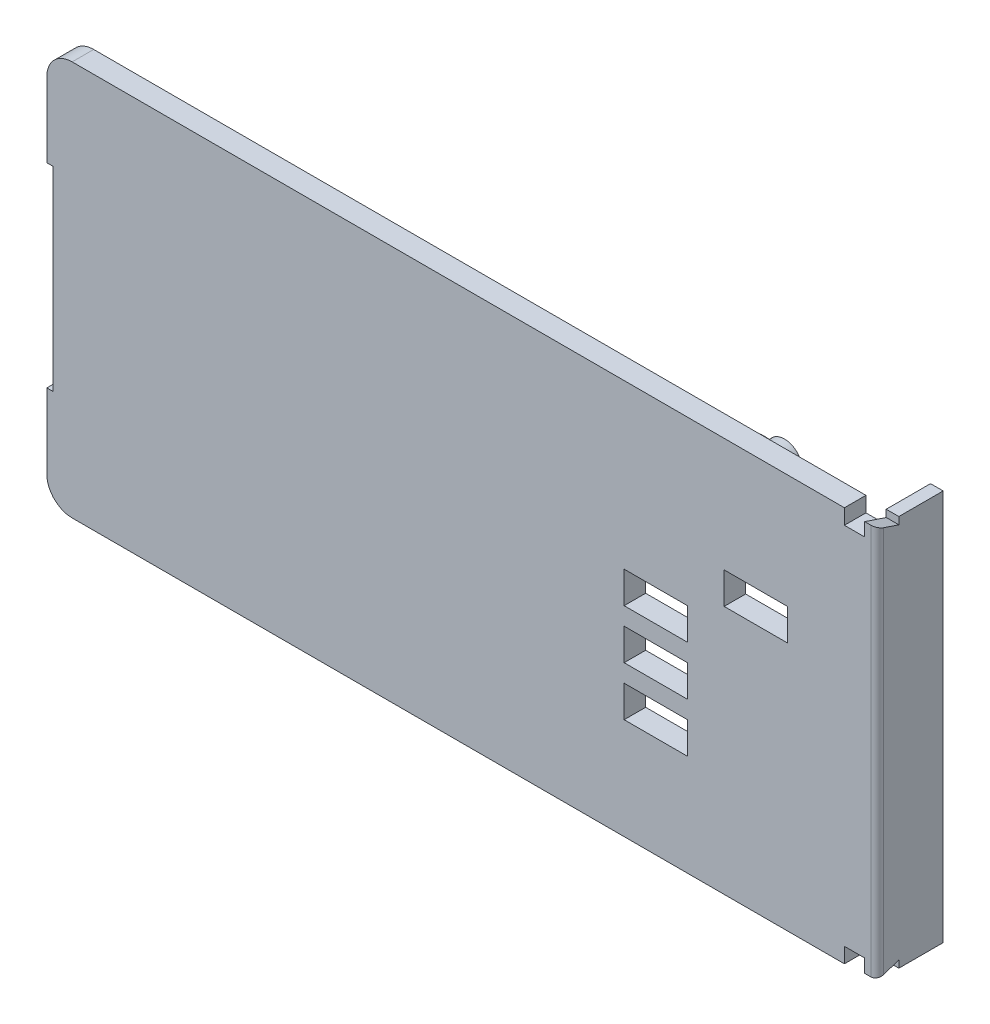
SolidWorks part; units mm, degrees
ref_plane "Front Plane" through (0, 0, 0) normal (0, 0, 1) x (1, 0, 0)
ref_plane "Top Plane" through (0, 0, 0) normal (0, 1, 0) x (1, 0, 0)
ref_plane "Right Plane" through (0, 0, 0) normal (1, 0, 0) x (0, 0, -1)
sketch "Sketch1" plane through (0, 0, 0) normal (0, 0, 1) x (1, 0, 0)
  line L0 (-32.3, 15.8) -> (-32.3, 7.5) construction
  line L1 (-32.1, 15.6) -> (30.9, 15.6)
  line L2 (-32.1, 15.6) -> (-32.1, 7.7)
  line L3 (-32.1, -15.6) -> (30.9, -15.6)
  line L4 (30.9, 15.6) -> (30.9, 14.4)
  line L5 (31.3, 15.8) -> (-32.3, 15.8) construction
  line L6 (-32.3, -15.8) -> (31.3, -15.8) construction
  line L7 (31.3, 15.8) -> (31.3, 14.8) construction
  line L8 (-32.1, 7.7) -> (-31.6, 7.7)
  line L9 (-31.6, 7.7) -> (-31.6, -7.7)
  line L10 (-31.6, -7.7) -> (-32.1, -7.7)
  line L11 (-31.8, 7.5) -> (-31.8, -7.5) construction
  line L12 (-31.8, 7.5) -> (-32.3, 7.5) construction
  line L13 (32.3, 15.8) -> (32.3, 14.8) construction
  line L14 (-32.1, -7.7) -> (-32.1, -15.6)
  line L15 (30.9, 14.4) -> (32.5008, 14.4)
  line L17 (32.5008, -14.4) -> (30.9, -14.4)
  line L18 (31.3, -14.8) -> (32.3, -14.8) construction
  line L19 (31.3, 14.8) -> (32.3, 14.8) construction
  line L20 (30.9, -14.4) -> (30.9, -15.6)
  line L21 (32.5008, 14.4) -> (32.5008, 15.45)
  line L22 (32.5008, 15.45) -> (33.5, 15.45)
  line L23 (33.5, 15.45) -> (33.5, -15.45)
  line L24 (33.5, -15.45) -> (32.5008, -15.45)
  line L25 (32.5008, -15.45) -> (32.5008, -14.4)
  line L26 (33.5, -15.8) -> (32.3, -15.8) construction
  line L27 (33.5, -16.5) -> (33.5, -15.8) construction
  line L28 (32.3, 15.8) -> (33.5, 15.8) construction
  point P12 (31.3, 15.3)
  point P19 (-31.8, 0)
  point P20 (-31.6, 0)
  dimension "D1" = 0.2
  dimension "D2" = 0.2
  dimension "D3" = 0.2
  dimension "D4" = 0.4
  dimension "D5" = 0.2
  dimension "D6" = 0.2
  dimension "D7" = 0.2
  dimension "D8" = 0.4
  dimension "D9" = 0.2008
  dimension "D10" = 0.35
  dimension "D11" = 0.35
  dimension "D12" = 0.4
extrude "Boss-Extrude1" add sketch "Sketch1" against normal offset from surface (1.7 mm away) 0.2 offset beyond the face yes
sketch "Sketch2" plane through (0, 0, -1.7) normal (0, 0, -1) x (-1, 0, 0)
  line L0 (32.1, 7.7) -> (32.1, 15.6) construction
  line L1 (32.1, 8.5791) -> (30.9, 8.5791)
  line L2 (32.1, 8.5791) -> (32.1, -8.7)
  line L3 (32.1, -8.7) -> (30.9, -8.7)
  line L4 (30.9, 8.5791) -> (30.9, -8.7)
  line L5 (31.6, -7.7) -> (31.6, 7.7) construction
  line L6 (32.1, -7.7) -> (31.6, -7.7) construction
  point P10 (32.1, -0.0604)
  point P11 (30.9, -0.0604)
  dimension "D1" = 0.7
  dimension "D2" = 1
extrude "Boss-Extrude2" add sketch "Sketch2" along normal offset from surface (3.5 mm away) 0.2
sketch "Sketch3" plane through (33.5, 0, 0) normal (1, 0, 0) x (0, 0, -1)
  line L0 (0, 15.45) -> (1.7, 14.8833)
  line L1 (0, -15.45) -> (0, 15.45) construction
  line L2 (1.7, 15.45) -> (1.7, -15.45) construction
  line L3 (1.7, 14.8833) -> (1.7, 15.45)
  line L4 (1.7, 15.45) -> (0, 15.45)
  line L5 (1.7, 15.45) -> (0, 15.45) construction
  line L6 (0, 15.8) -> (1.5, 15.3) construction
  line M1 (1.7, -15.45) -> (1.7, 15.45)
  line M2 (1.7, 15.45) -> (0, 15.45)
extrude "Cut-Extrude1" cut sketch "Sketch3" against normal up to surface (1.2 mm away) contours L0 M2 M1 region at (33.5, 15.2611, -1.1333)
mirror "Mirror1" about plane through (0, 0, 0) normal (0, 1, 0) of "Cut-Extrude1"
sketch "Sketch4" plane through (0, 0, -1.7) normal (0, 0, -1) x (-1, 0, 0)
  line L1 (-33.5, -15.45) -> (-32.5008, -15.45)
  line L2 (-33.5, -15.45) -> (-33.5, 15.45)
  line L3 (-33.5, 15.45) -> (-32.5008, 15.45)
  line L4 (-32.5008, -15.45) -> (-32.5008, 15.45)
extrude "Boss-Extrude3" add sketch "Sketch4" along normal offset from surface (3.5 mm away) 0.2
fillet "Fillet1" radius 2 2 edges at (-32.1, -15.6, -0.85) (-32.1, 15.6, -0.85)
fillet "Fillet2" radius 0.5 1 edges at (33.5, 0, 0)
sketch "Sketch5" plane through (0, 0, -1.7) normal (0, 0, -1) x (-1, 0, 0)
  line L0 (-27.9, -17) -> (30.9204, -17) construction
  line L1 (-13.5, -7.6) -> (-18.5, -7.6)
  line L2 (-13.5, -7.6) -> (-13.5, -5.1)
  line L3 (-13.5, -5.1) -> (-18.5, -5.1)
  line L4 (-18.5, -7.6) -> (-18.5, -5.1)
  line L5 (-33.5, 15.45) -> (-33.5, -15.45) construction
  line L6 (-13.5, -3.7) -> (-18.5, -3.7)
  line L7 (-13.5, -3.7) -> (-13.5, -1.2)
  line L8 (-13.5, -1.2) -> (-18.5, -1.2)
  line L9 (-18.5, -3.7) -> (-18.5, -1.2)
  line L10 (-13.5, 0.2) -> (-18.5, 0.2)
  line L11 (-13.5, 0.2) -> (-13.5, 2.7)
  line L12 (-13.5, 2.7) -> (-18.5, 2.7)
  line L13 (-18.5, 0.2) -> (-18.5, 2.7)
  line L15 (-21.4, 4.1) -> (-26.4, 4.1)
  line L16 (-21.4, 4.1) -> (-21.4, 6.6)
  line L17 (-21.4, 6.6) -> (-26.4, 6.6)
  line L18 (-26.4, 4.1) -> (-26.4, 6.6)
  dimension "D1" = 2.5
  dimension "D2" = 5
  dimension "D3" = 9.4
  dimension "D4" = 15
  dimension "D6" = 7.9
  dimension "D7" = 3.9
  dimension "D8" = 3.9
  dimension "D5" = 3
extrude "Cut-Extrude2" cut sketch "Sketch5" against normal through all
sketch "Sketch6" plane through (0, 0, -1.7) normal (0, 0, -1) x (-1, 0, 0)
  line L0 (30.9, 8.5791) -> (30.9, -8.7) construction
  line L1 (17.508, -5.0604) -> (7.508, -5.0604)
  line L2 (17.508, -5.0604) -> (17.508, 4.9396)
  line L3 (17.508, 4.9396) -> (7.508, 4.9396)
  line L4 (7.508, -5.0604) -> (7.508, 4.9396)
  line L5 (29.008, 14.508) -> (29.008, -14.508) construction
  point P6 (30.9, -0.0604)
  point P7 (17.508, -0.0604)
  dimension "D1" = 10
  dimension "D2" = 11.5
extrude "Extrude-Thin1" add sketch "Sketch6" along normal offset from surface (2.3 mm away) 4.7 thin thin type one direction reverse wall 1
sketch "Sketch7" plane through (0, 0, -1.7) normal (0, 0, -1) x (-1, 0, 0)
  line L0 (-4.77, -12.4817) -> (-7.31, -12.4817) construction
  line L1 (-4.77, -12.4817) -> (-4.77, -9.9417) construction
  circle A0 centre (-4.77, -12.4817) radius 0.25
  circle A1 centre (-7.31, -12.4817) radius 0.25
  circle A2 centre (-9.85, -12.4817) radius 0.25
  circle A3 centre (-12.39, -12.4817) radius 0.25
  circle A4 centre (-14.93, -12.4817) radius 0.25
  circle A5 centre (-17.47, -12.4817) radius 0.25
  circle A6 centre (-20.01, -12.4817) radius 0.25
  circle A7 centre (-22.55, -12.4817) radius 0.25
  circle A8 centre (-25.09, -12.4817) radius 0.25
  circle A9 centre (-27.63, -12.4817) radius 0.25
  circle A10 centre (-7.31, -9.9417) radius 0.25
  circle A11 centre (-9.85, -9.9417) radius 0.25
  circle A12 centre (-12.39, -9.9417) radius 0.25
  circle A13 centre (-14.93, -9.9417) radius 0.25
  circle A14 centre (-17.47, -9.9417) radius 0.25
  circle A15 centre (-20.01, -9.9417) radius 0.25
  circle A16 centre (-22.55, -9.9417) radius 0.25
  circle A17 centre (-25.09, -9.9417) radius 0.25
  circle A18 centre (-27.63, -9.9417) radius 0.25
  circle A19 centre (-7.31, -7.4017) radius 0.25
  circle A20 centre (-9.85, -7.4017) radius 0.25
  circle A21 centre (-12.39, -7.4017) radius 0.25
  circle A22 centre (-14.93, -7.4017) radius 0.25
  circle A23 centre (-17.47, -7.4017) radius 0.25
  circle A24 centre (-20.01, -7.4017) radius 0.25
  circle A25 centre (-22.55, -7.4017) radius 0.25
  circle A26 centre (-25.09, -7.4017) radius 0.25
  circle A27 centre (-27.63, -7.4017) radius 0.25
  circle A28 centre (-7.31, -4.8617) radius 0.25
  circle A29 centre (-9.85, -4.8617) radius 0.25
  circle A30 centre (-12.39, -4.8617) radius 0.25
  circle A31 centre (-14.93, -4.8617) radius 0.25
  circle A32 centre (-17.47, -4.8617) radius 0.25
  circle A33 centre (-20.01, -4.8617) radius 0.25
  circle A34 centre (-22.55, -4.8617) radius 0.25
  circle A35 centre (-25.09, -4.8617) radius 0.25
  circle A36 centre (-27.63, -4.8617) radius 0.25
  circle A37 centre (-7.31, -2.3217) radius 0.25
  circle A38 centre (-9.85, -2.3217) radius 0.25
  circle A39 centre (-12.39, -2.3217) radius 0.25
  circle A40 centre (-14.93, -2.3217) radius 0.25
  circle A41 centre (-17.47, -2.3217) radius 0.25
  circle A42 centre (-20.01, -2.3217) radius 0.25
  circle A43 centre (-22.55, -2.3217) radius 0.25
  circle A44 centre (-25.09, -2.3217) radius 0.25
  circle A45 centre (-27.63, -2.3217) radius 0.25
  circle A46 centre (-7.31, 0.2183) radius 0.25
  circle A47 centre (-9.85, 0.2183) radius 0.25
  circle A48 centre (-12.39, 0.2183) radius 0.25
  circle A49 centre (-14.93, 0.2183) radius 0.25
  circle A50 centre (-17.47, 0.2183) radius 0.25
  circle A51 centre (-20.01, 0.2183) radius 0.25
  circle A52 centre (-22.55, 0.2183) radius 0.25
  circle A53 centre (-25.09, 0.2183) radius 0.25
  circle A54 centre (-27.63, 0.2183) radius 0.25
  circle A55 centre (-7.31, 2.7583) radius 0.25
  circle A56 centre (-9.85, 2.7583) radius 0.25
  circle A57 centre (-12.39, 2.7583) radius 0.25
  circle A58 centre (-14.93, 2.7583) radius 0.25
  circle A59 centre (-17.47, 2.7583) radius 0.25
  circle A60 centre (-20.01, 2.7583) radius 0.25
  circle A61 centre (-22.55, 2.7583) radius 0.25
  circle A62 centre (-25.09, 2.7583) radius 0.25
  circle A63 centre (-27.63, 2.7583) radius 0.25
  circle A64 centre (-7.31, 5.2983) radius 0.25
  circle A65 centre (-9.85, 5.2983) radius 0.25
  circle A66 centre (-12.39, 5.2983) radius 0.25
  circle A67 centre (-14.93, 5.2983) radius 0.25
  circle A68 centre (-17.47, 5.2983) radius 0.25
  circle A69 centre (-20.01, 5.2983) radius 0.25
  circle A70 centre (-22.55, 5.2983) radius 0.25
  circle A71 centre (-25.09, 5.2983) radius 0.25
  circle A72 centre (-27.63, 5.2983) radius 0.25
  circle A73 centre (-7.31, 7.8383) radius 0.25
  circle A74 centre (-9.85, 7.8383) radius 0.25
  circle A75 centre (-12.39, 7.8383) radius 0.25
  circle A76 centre (-14.93, 7.8383) radius 0.25
  circle A77 centre (-17.47, 7.8383) radius 0.25
  circle A78 centre (-20.01, 7.8383) radius 0.25
  circle A79 centre (-22.55, 7.8383) radius 0.25
  circle A80 centre (-25.09, 7.8383) radius 0.25
  circle A81 centre (-27.63, 7.8383) radius 0.25
  circle A82 centre (-7.31, 10.3783) radius 0.25
  circle A83 centre (-9.85, 10.3783) radius 0.25
  circle A84 centre (-12.39, 10.3783) radius 0.25
  circle A85 centre (-14.93, 10.3783) radius 0.25
  circle A86 centre (-17.47, 10.3783) radius 0.25
  circle A87 centre (-20.01, 10.3783) radius 0.25
  circle A88 centre (-22.55, 10.3783) radius 0.25
  circle A89 centre (-25.09, 10.3783) radius 0.25
  circle A90 centre (-27.63, 10.3783) radius 0.25
  circle A91 centre (-4.77, -9.9417) radius 0.25
  circle A92 centre (-4.77, -7.4017) radius 0.25
  circle A93 centre (-4.77, -4.8617) radius 0.25
  circle A94 centre (-4.77, -2.3217) radius 0.25
  circle A95 centre (-4.77, 0.2183) radius 0.25
  circle A96 centre (-4.77, 2.7583) radius 0.25
  circle A97 centre (-4.77, 5.2983) radius 0.25
  circle A98 centre (-4.77, 7.8383) radius 0.25
  circle A99 centre (-4.77, 10.3783) radius 0.25
  point P2 (-4.77, -12.4817)
  dimension "D1" = 0.5
  dimension "D4" = 2.54
  dimension "D5" = 2.54
  dimension "D2" = 10
  dimension "D3" = 10
sketch "Sketch8" plane through (0, 0, -1.7) normal (0, 0, -1) x (-1, 0, 0)
  circle A0 centre (-22.55, -9.9417) radius 1.4
  circle A1 centre (-17.47, 7.8383) radius 1.4
  dimension "D1" = 2.8
extrude "Boss-Extrude4" add sketch "Sketch8" along normal up to surface (7 mm away)
extrude "Extrude-Thin2" add sketch "Sketch8<2>" along normal offset from surface (5.4 mm away) 1.6 thin thin type one direction wall 1
sketch "Sketch8<2>" plane through (0, 0, -1.7) normal (0, 0, -1) x (-1, 0, 0) same geometry as "Sketch8"
